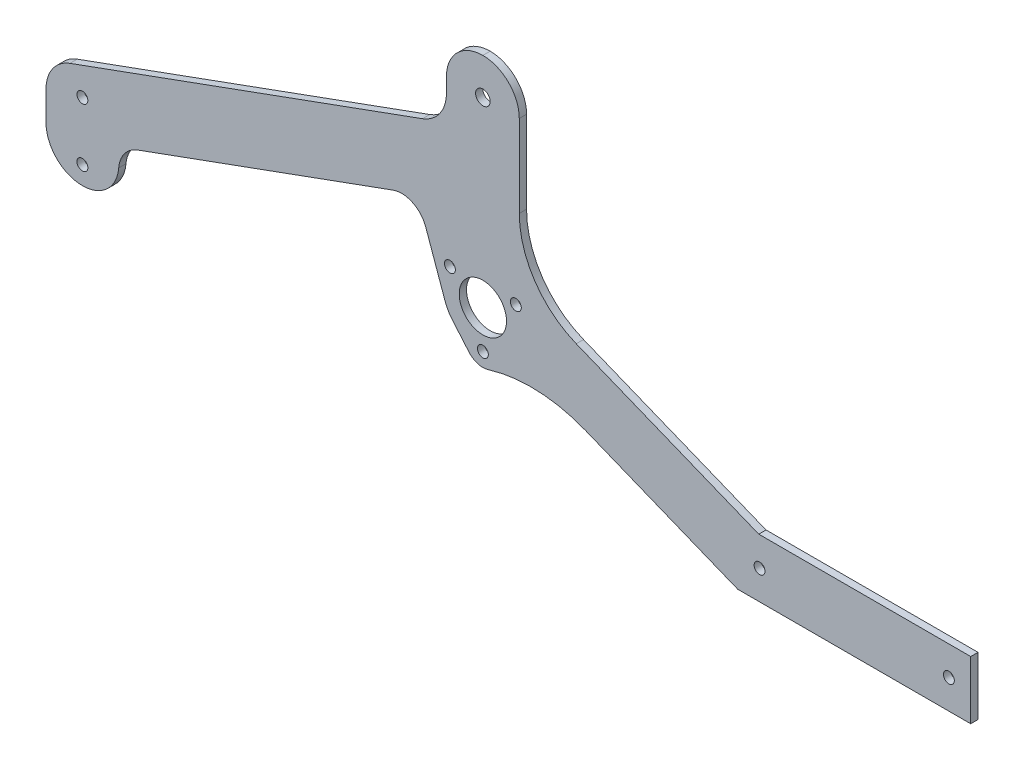
SolidWorks part; units mm, degrees
ref_plane "Спереди" through (0, 0, 0) normal (0, 0, 1) x (1, 0, 0)
ref_plane "Сверху" through (0, 0, 0) normal (0, 1, 0) x (1, 0, 0)
ref_plane "Справа" through (0, 0, 0) normal (1, 0, 0) x (0, 0, -1)
sketch "эскиз" plane through (0, 0, 0) normal (0, 0, 1) x (1, 0, 0)
  line L0 (110, -110) -> (110, -24) construction
  line L1 (-35, -110) -> (-35, -24) construction
  line L2 (-180, -24) -> (-146, -24) construction
  line L3 (-180, -110) -> (-35, -110) construction
  line L4 (-180, -24) -> (-198, -24) construction
  line L5 (-35, -110) -> (110, -110) construction
  line L6 (-180, -110) -> (-180, -24) construction
  line L7 (76, -24) -> (110, -24) construction
  line L8 (128, -24) -> (110, -24) construction
  line L10 (-180, -24) -> (-110, -24) construction
  line L11 (-110, -24) -> (-35, -24) construction
  line L12 (-110, -24) -> (0, 0) construction
  line L13 (0, 0) -> (110, -24) construction
  line L14 (-110, -24) -> (-110, -5) construction
  circle A0 centre (-180, -110) radius 57.5 construction
  circle A1 centre (-35, -110) radius 57.5 construction
  circle A2 centre (110, -110) radius 57.5 construction
  circle A3 centre (-198, -24) radius 1.5 construction
  circle A4 centre (-146, -24) radius 1.5 construction
  circle A5 centre (76, -24) radius 1.5 construction
  circle A6 centre (128, -24) radius 1.5 construction
  circle A7 centre (-69, -24) radius 1.5 construction
  circle A8 centre (-17, -24) radius 1.5 construction
  circle A9 centre (-110, -5) radius 1.5
  circle A10 centre (-110, -21) radius 1.5
  circle A11 centre (-110, -36) radius 2
  circle A12 centre (0, 50) radius 2
  point P31 (-163, -24)
  dimension "D1" = 115
  dimension "D4" = 3
  dimension "D7" = 34
  dimension "D12" = 3
  dimension "D11" = 4
  dimension "D17" = 4
  dimension "D19" = 18
  dimension "D2" = 145
  dimension "D3" = 86
  dimension "D5" = 18
  dimension "D6" = 34
  dimension "D8" = 70
  dimension "D9" = 145
  dimension "D10" = 35
  dimension "D13" = 16
  dimension "D14" = 12
  dimension "D15" = 110
  dimension "D16" = 15
  dimension "D18" = 50
sketch "эскиз 1" plane through (0, 0, 0) normal (0, 0, 1) x (1, 0, 0)
  line L0 (-204, -16) -> (-204, -32)
  line L1 (-204, -32) -> (-134, -32)
  line L2 (-134, -32) -> (-134, -47)
  line L3 (-204, -16) -> (-126.1949, -16)
  line L4 (-35, -110) -> (110, -110) construction
  line L5 (-11, -32) -> (-11, -16)
  line L6 (-134, -47) -> (-86, -47)
  line L9 (-116.245, -27) -> (-103.755, -27)
  line L10 (-86, -32) -> (-86, -47)
  line L11 (-35, -16) -> (-35, -110) construction
  line L12 (-86, -32) -> (-11, -32)
  line L13 (-11, -32) -> (-86, -32)
  line L14 (-120, -26) -> (-100, -26) construction
  line L15 (-93.8051, -16) -> (-11, -16)
  line L16 (-110, -24) -> (-110, -5) construction
  line L17 (-35, -110) -> (-35, -24) construction
  line L18 (-180, -16) -> (-180, -32) construction
  line L19 (-180, -110) -> (-180, -24) construction
  line L20 (-180, -24) -> (-198, -24) construction
  line L21 (-110, -27) -> (-110, -47) construction
  line L22 (-120, -27) -> (-120, -16) construction
  line L23 (-100, -26.2682) -> (-100, -16) construction
  line L24 (-126.1949, -16) -> (-126.1949, -27) construction
  line L25 (-126.1949, -27) -> (-93.8051, -27) construction
  line L26 (-93.8051, -27) -> (-93.8051, -16) construction
  circle A0 centre (-198, -24) radius 1.5
  circle A1 centre (-146, -24) radius 1.5
  circle A2 centre (-110, -36) radius 2
  circle A3 centre (-69, -24) radius 1.5
  circle A4 centre (-17, -24) radius 1.5
  circle A5 centre (-17, -24) radius 1.5 construction
  circle A6 centre (-69, -24) radius 1.5 construction
  circle A7 centre (-110, -36) radius 2 construction
  circle A8 centre (-146, -24) radius 1.5 construction
  circle A9 centre (-198, -24) radius 1.5 construction
  circle A10 centre (-110, -16) radius 10 construction
  circle A11 centre (-110, -36) radius 20 construction
  arc A12 (-103.755, -27) -> (-93.8051, -16) centre (-103.755, -17) ccw
  arc A13 (-116.245, -27) -> (-126.1949, -16) centre (-116.245, -17) cw
  point P25 (-110, -47)
  dimension "D6" = 9
  dimension "D5" = 20
  dimension "D1" = 24
  dimension "D2" = 24
  dimension "D3" = 16
  dimension "D4" = 11
  dimension "D7" = 70
  dimension "D8" = 8
  dimension "D9" = 5
extrude "тело маленькой арки" [suppressed] add sketch "эскиз 1" along normal blind 2
fillet "Скругление2" [suppressed] radius 10
fillet "Скругление3" [suppressed] radius 15
fillet "Скругление16" [suppressed] radius 8
sketch "Эскиз1" plane through (0, 0, 0) normal (0, 0, 1) x (1, 0, 0)
  line L0 (10, 10.5395) -> (75.7787, -16)
  line L1 (75.7787, -16) -> (134, -16)
  line L2 (134, -16) -> (134, -32)
  line L3 (134, -32) -> (70, -32)
  line L4 (70, -32) -> (8.372, -7.1351)
  line L6 (-12.7222, 2.951) -> (-18.0725, 18.0096)
  line L7 (10, 10.5395) -> (10, 60)
  line L8 (-113.4202, 1.3969) -> (-10, 39.0388)
  line L9 (-120, -16) -> (-120, -8)
  line L10 (-12.7222, 2.951) -> (-10.3652, -3.6828)
  line L11 (-100, -11.8095) -> (-18.0725, 18.0096)
  line L12 (-8.9167, 9.5422) -> (-1.9932, 10.8179) construction
  line L13 (110, -110) -> (110, -24) construction
  line L14 (3.8054, -12.4932) -> (8.372, -7.1351)
  line L15 (-3.8054, -12.4932) -> (-8.372, -7.1351)
  line L16 (-120, -26) -> (-100, -26) construction
  line L17 (-100, -16) -> (-100, -11.8095)
  line L18 (-110, -5) -> (-110, -26) construction
  line L19 (-110, -24) -> (-110, -5) construction
  line L20 (8.9167, 9.5422) -> (1.9932, 10.8179) construction
  line L21 (-100, -26) -> (-100, -16) construction
  line L22 (10, 60) -> (-10, 60)
  line L23 (-120, 2) -> (-100, 2) construction
  line L24 (-10, 60) -> (-10, 39.0388)
  line L27 (12.7222, 2.951) -> (10.3652, -3.6828) construction
  line L31 (-120, -16) -> (-120, -26) construction
  circle A0 centre (-110, -21) radius 1.5
  circle A1 centre (-110, -5) radius 1.5
  circle A2 centre (-110, -5) radius 1.5 construction
  circle A3 centre (-110, -21) radius 1.5 construction
  circle A4 centre (0, 0) radius 6.5
  circle A5 centre (0, 0) radius 11 construction
  arc A6 (-8.9167, 9.5422) -> (-12.7222, 2.951) centre (-8.0107, 4.625) ccw construction
  arc A7 (1.9932, 10.8179) -> (-1.9932, 10.8179) centre (0, 0) ccw construction
  arc A8 (-3.8054, -12.4932) -> (3.8054, -12.4932) centre (0, -9.25) ccw
  arc A9 (12.7222, 2.951) -> (8.9167, 9.5422) centre (8.0107, 4.625) ccw construction
  arc A10 (8.372, -7.1351) -> (10.3652, -3.6828) centre (0, 0) ccw construction
  arc A11 (-10.3652, -3.6828) -> (-8.372, -7.1351) centre (0, 0) ccw
  circle A12 centre (0, 0) radius 9.25 construction
  circle A13 centre (0, -10.45) radius 1.5
  circle A14 centre (-9.05, 5.225) radius 1.5
  circle A15 centre (9.05, 5.225) radius 1.5
  circle A16 centre (0, 0) radius 7.65 construction
  circle A17 centre (128, -24) radius 1.5
  circle A18 centre (76, -24) radius 1.5
  circle A19 centre (76, -24) radius 1.5 construction
  circle A20 centre (128, -24) radius 1.5 construction
  circle A21 centre (0, 50) radius 2
  circle A22 centre (0, 50) radius 2 construction
  arc A23 (-120, -16) -> (-100, -16) centre (-110, -16) ccw
  arc A24 (-113.4202, 1.3969) -> (-120, -8) centre (-110, -8) ccw
  point P27 (134, -24)
  point P33 (0, 60)
  point P62 (0, 0)
  point P68 (0, 0)
  dimension "D2" = 13
  dimension "D3" = 3
  dimension "D5" = 5
  dimension "D6" = 18.5
  dimension "D7" = 22
  dimension "D14" = 3
  dimension "D17" = 15.3
  dimension "D18" = 7
  dimension "D20" = 20
  dimension "D13" = 17
  dimension "D22" = 20
  dimension "D4" = 20
  dimension "D11" = 10
  dimension "D16" = 17
  dimension "D1" = 16
  dimension "D8" = 10
  dimension "D9" = 6
  dimension "D10" = 24
  dimension "D15" = 3
  dimension "D19" = 10.45
  dimension "D21" = 5
extrude "тело большой арки" add sketch "Эскиз1" along normal blind 2
fillet "Скругление7" radius 7 1 edges at (-18.0725, 18.0096, 1)
fillet "Скругление8" radius 40 1 edges at (8.372, -7.1351, 1)
fillet "Скругление9" radius 10 3 edges at (-10, 39.0388, 1) (10, 60, 1) (-10, 60, 1)
fillet "Скругление10" radius 25 1 edges at (10, 10.5395, 1)
fillet "Скругление17" radius 8 1 edges at (-100, -11.8095, 1)
fillet "Скругление18" [suppressed] radius 3
